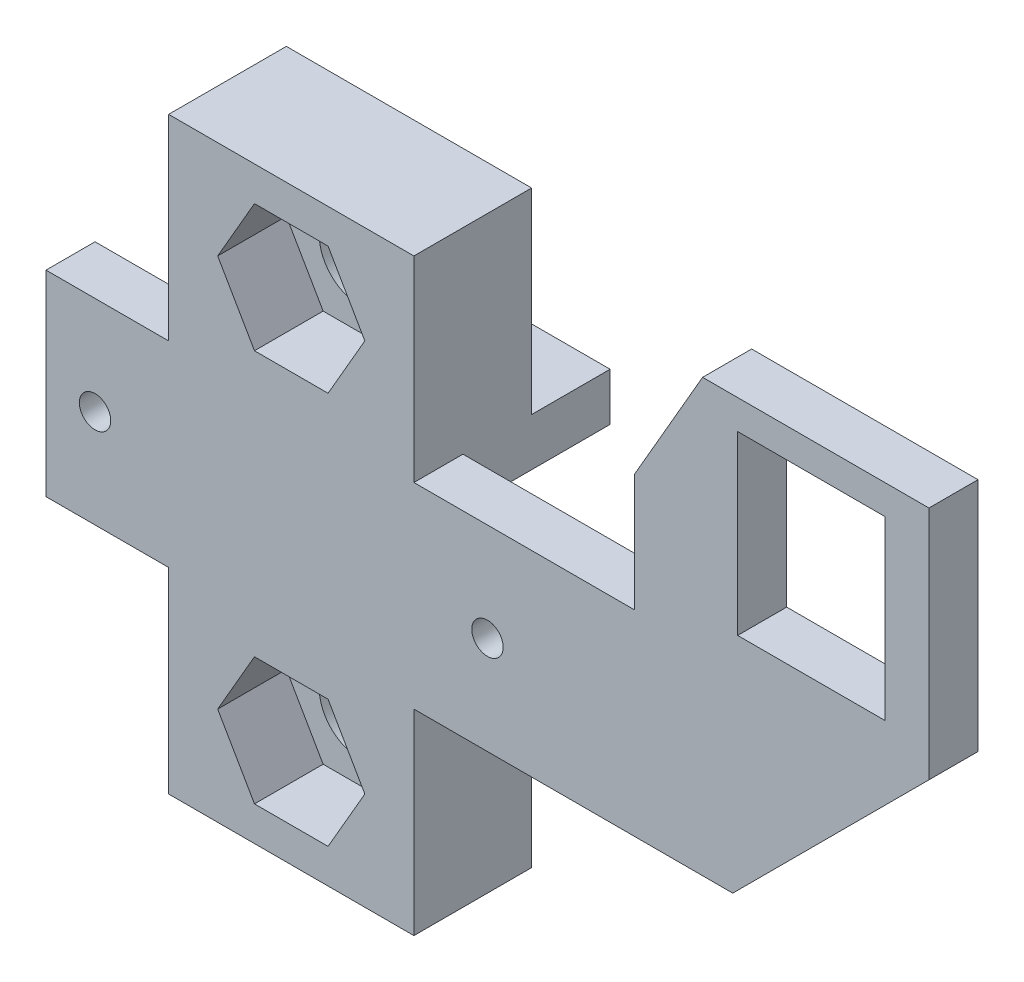
SolidWorks part; units mm, degrees
ref_plane "Спереди" through (0, 0, 0) normal (0, 0, 1) x (1, 0, 0)
ref_plane "Сверху" through (0, 0, 0) normal (0, 1, 0) x (1, 0, 0)
ref_plane "Справа" through (0, 0, 0) normal (1, 0, 0) x (0, 0, -1)
sketch "Sketch2" plane through (0, 0, 0) normal (0, 0, 1) x (1, 0, 0)
  line L1 (12.5, -10) -> (-12.5, -10)
  line L2 (12.5, -10) -> (12.5, 10)
  line L3 (12.5, 10) -> (-12.5, 10)
  line L4 (-12.5, -10) -> (-12.5, 10)
  line L5 (12.5, -10) -> (-12.5, 10) construction
  line L6 (12.5, 10) -> (-12.5, -10) construction
  point P0 (0, 0)
  dimension "D1" = 25
  dimension "D2" = 20
extrude "Boss-Extrude1" add sketch "Sketch2" along normal blind 30
sketch "Sketch3" plane through (-12.5, 0, 0) normal (-1, 0, 0) x (0, 0, 1)
  line L0 (30, 0) -> (0, 0) construction
  line L1 (30, 10) -> (30, -10) construction
  line L2 (0, 10) -> (0, -10) construction
  line L4 (4.875, -5.125) -> (25.125, -5.125)
  line L5 (4.875, -5.125) -> (4.875, 5.125)
  line L6 (4.875, 5.125) -> (25.125, 5.125)
  line L7 (25.125, -5.125) -> (25.125, 5.125)
  line L8 (4.875, -5.125) -> (25.125, 5.125) construction
  line L9 (4.875, 5.125) -> (25.125, -5.125) construction
  point P6 (15, 0)
  dimension "D1" = 10.25
  dimension "D2" = 20.25
extrude "Cut-Extrude1" cut sketch "Sketch3" against normal through all
sketch "Sketch4" plane through (0, 0, 30) normal (0, 0, 1) x (1, 0, 0)
  line L1 (25, -10) -> (-25, -10)
  line L2 (25, -10) -> (25, 10)
  line L3 (25, 10) -> (-25, 10)
  line L4 (-25, -10) -> (-25, 10)
  line L5 (25, -10) -> (-25, 10) construction
  line L6 (25, 10) -> (-25, -10) construction
  point P0 (0, 0)
  dimension "D1" = 20
  dimension "D2" = 50
extrude "Boss-Extrude2" add sketch "Sketch4" along normal blind 5
sketch "Sketch6" plane through (0, 0, 35) normal (0, 0, 1) x (1, 0, 0)
  line L0 (-25, 0) -> (25, 0) construction
  line L1 (-25, 10) -> (-25, -10) construction
  line L2 (25, -10) -> (25, 10) construction
  circle A0 centre (-20, 0) radius 1.6
  circle A1 centre (20, 0) radius 1.6
  point P10 (0, 0)
  dimension "D3" = 3.2
  dimension "D1" = 40
  dimension "D2" = 20
extrude "Cut-Extrude2" cut sketch "Sketch6" against normal through all
sketch "Sketch9" plane through (25, 0, 0) normal (1, 0, 0) x (0, 0, -1)
  line L0 (-35, 10) -> (-30, -10) construction
  line L2 (-30, 10) -> (-35, 10)
  line L3 (-30, 10) -> (-30, -10)
  line L4 (-30, -10) -> (-35, -10)
  line L5 (-35, 10) -> (-35, -10)
  line L6 (-30, 10) -> (-35, -10) construction
  line L7 (-30, -10) -> (-35, 10) construction
  point P4 (-32.5, 0)
extrude "Boss-Extrude3" add sketch "Sketch9" along normal blind 40
sketch "Sketch14" plane through (0, 0, 35) normal (0, 0, 1) x (1, 0, 0)
  line L0 (65, 10) -> (65, 34)
  line L1 (65, 34) -> (35, 34)
  line L2 (35, 34) -> (35, 10)
  line L3 (65, 10) -> (-25, 10) construction
  line L4 (35, 10) -> (65, 10)
  dimension "D1" = 30
  dimension "D2" = 24
extrude "Boss-Extrude5" add sketch "Sketch14" against normal up to vertex (5 mm away) up to point (12.5, 10, 30)
sketch "Sketch19" plane through (0, 0, 35) normal (0, 0, 1) x (1, 0, 0)
  line L0 (35, 22) -> (65, 22) construction
  line L1 (35, 10) -> (65, 10) construction
  line L2 (35, 34) -> (35, 10) construction
  line L3 (60.5, 31) -> (45.5, 31)
  line L4 (60.5, 31) -> (60.5, 13)
  line L5 (60.5, 13) -> (45.5, 13)
  line L6 (45.5, 31) -> (45.5, 13)
  line L7 (60.5, 31) -> (45.5, 13) construction
  line L8 (65, 34) -> (65, -10) construction
  line L9 (60.5, 13) -> (45.5, 31) construction
  point P5 (53, 22)
  dimension "D1" = 15
  dimension "D2" = 18
  dimension "D3" = 12
extrude "Cut-Extrude5" cut sketch "Sketch19" against normal through all
chamfer "Chamfer1" distance 12 angle 30 1 edges at (35, 34, 32.5) first distance on face at (35, 22, 32.5)
chamfer "Chamfer2" distance 20 angle 45 1 edges at (65, -10, 32.5)
sketch "Sketch20" plane through (0, 10, 0) normal (0, 1, 0) x (1, 0, 0)
  line L0 (0, 0) -> (0, -35) construction
  line L1 (12.5, 0) -> (-12.5, 0) construction
  line L2 (35, -35) -> (-25, -35) construction
  line L4 (-12.5, -26) -> (12.5, -26)
  line L5 (-12.5, -26) -> (-12.5, -35)
  line L6 (-12.5, -35) -> (12.5, -35)
  line L7 (12.5, -26) -> (12.5, -35)
  line L8 (-12.5, -26) -> (12.5, -35) construction
  line L9 (-12.5, -35) -> (12.5, -26) construction
  point P6 (0, -30.5)
  dimension "D1" = 9
extrude "Boss-Extrude6" add sketch "Sketch20" along normal blind 20 and the other way blind 40
sketch "Sketch21" plane through (0, 0, 0) normal (0, 0, -1) x (-1, 0, 0)
  line L0 (12.5, 0) -> (-12.5, 0) construction
  line L1 (12.5, 10) -> (12.5, -10) construction
  line L2 (-12.5, -10) -> (-12.5, 10) construction
  line L4 (-12.5, -10) -> (12.5, -10)
  line L5 (-12.5, -10) -> (-12.5, 10)
  line L6 (-12.5, 10) -> (12.5, 10)
  line L7 (12.5, -10) -> (12.5, 10)
  line L8 (-12.5, -10) -> (12.5, 10) construction
  line L9 (-12.5, 10) -> (12.5, -10) construction
  point P6 (0, 0)
extrude "Cut-Extrude6" cut sketch "Sketch21" against normal blind 15
sketch "Sketch22" plane through (0, 0, 35) normal (0, 0, 1) x (1, 0, 0)
  line L0 (0, 30) -> (0, -30) construction
  line L1 (-12.5, 30) -> (12.5, 30) construction
  line L2 (-12.5, -30) -> (12.5, -30) construction
  line L4 (7.5, 20) -> (3.75, 26.4952)
  line L5 (3.75, 26.4952) -> (-3.75, 26.4952)
  line L6 (-3.75, 26.4952) -> (-7.5, 20)
  line L7 (-7.5, 20) -> (-3.75, 13.5048)
  line L8 (-3.75, 13.5048) -> (3.75, 13.5048)
  line L9 (3.75, 13.5048) -> (7.5, 20)
  line L10 (7.5, -20) -> (3.75, -13.5048)
  line L11 (3.75, -13.5048) -> (-3.75, -13.5048)
  line L12 (-3.75, -13.5048) -> (-7.5, -20)
  line L13 (-7.5, -20) -> (-3.75, -26.4952)
  line L14 (-3.75, -26.4952) -> (3.75, -26.4952)
  line L15 (3.75, -26.4952) -> (7.5, -20)
  circle A0 centre (0, 20) radius 7.5 construction
  circle A1 centre (0, -20) radius 7.5 construction
  point P15 (0, 0)
  dimension "D1" = 40
  dimension "D3" = 15
  dimension "D2" = 20
extrude "Cut-Extrude7" cut sketch "Sketch22" against normal blind 7
sketch "Sketch23" plane through (0, 0, 26) normal (0, 0, -1) x (-1, 0, 0)
  line L0 (12.5, 20) -> (-12.5, 20) construction
  line L1 (12.5, 10) -> (12.5, 30) construction
  line L2 (-12.5, 10) -> (-12.5, 30) construction
  line L3 (12.5, -20) -> (-12.5, -20) construction
  line L4 (12.5, -30) -> (12.5, -10) construction
  line L5 (-12.5, -30) -> (-12.5, -10) construction
  line L7 (-12.5, 10) -> (12.5, 10)
  line L8 (-12.5, 10) -> (-12.5, 30)
  line L9 (-12.5, 30) -> (12.5, 30)
  line L10 (12.5, 10) -> (12.5, 30)
  line L11 (-12.5, 10) -> (12.5, 30) construction
  line L12 (-12.5, 30) -> (12.5, 10) construction
  line L13 (-12.5, -10) -> (12.5, -10)
  line L14 (-12.5, -10) -> (-12.5, -30)
  line L15 (-12.5, -30) -> (12.5, -30)
  line L16 (12.5, -10) -> (12.5, -30)
  line L17 (-12.5, -10) -> (12.5, -30) construction
  line L18 (-12.5, -30) -> (12.5, -10) construction
  point P12 (0, 20)
  point P18 (0, -20)
extrude "Boss-Extrude7" add sketch "Sketch23" along normal blind 3
sketch "Sketch24" plane through (0, 0, 28) normal (0, 0, 1) x (1, 0, 0)
  line L0 (7.5, 20) -> (-7.5, 20) construction
  line L1 (7.5, -20) -> (-7.5, -20) construction
  circle A0 centre (0, 20) radius 4.15
  circle A1 centre (0, -20) radius 4.15
  dimension "D1" = 8.3
extrude "Cut-Extrude8" cut sketch "Sketch24" against normal through all
